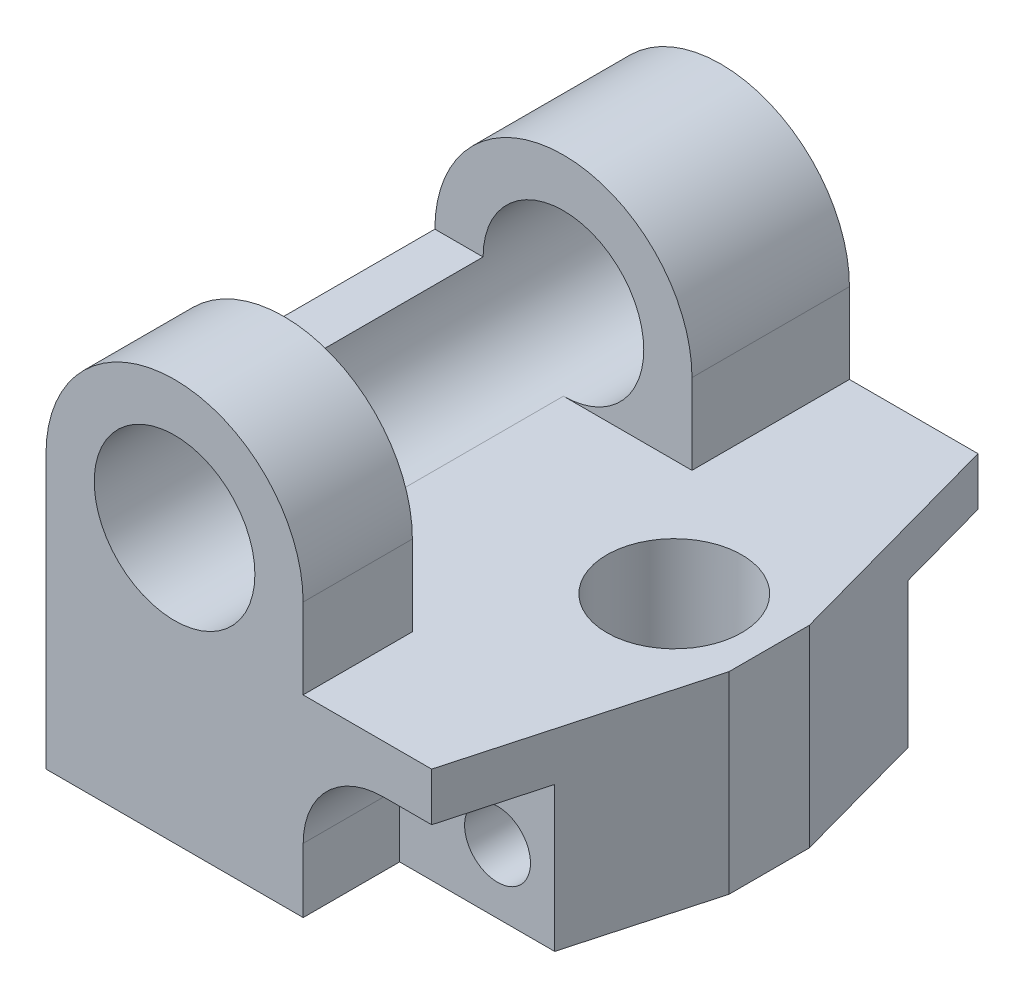
SolidWorks part; units mm, degrees
ref_plane "前视基准面" through (0, 0, 0) normal (0, 0, 1) x (1, 0, 0)
ref_plane "上视基准面" through (0, 0, 0) normal (0, 1, 0) x (1, 0, 0)
ref_plane "右视基准面" through (0, 0, 0) normal (1, 0, 0) x (0, 0, -1)
sketch "草图1" plane through (0, 0, 0) normal (0, 0, 1) x (1, 0, 0)
  line L0 (0, 0) -> (0, 2.5)
  line L2 (0, 0) -> (0, -6)
  line L3 (0, -6) -> (14, -6)
  line L4 (14, 0) -> (14, -6)
  line L5 (8, 2.5) -> (8, 0)
  line L6 (8, 0) -> (14, 0)
  circle A0 centre (4, 2.5) radius 2.5
  arc A1 (8, 2.5) -> (0, 2.5) centre (4, 2.5) ccw
  dimension "D1" = 14
  dimension "D2" = 6
extrude "凸台-拉伸1" add sketch "草图1" along normal mid plane 17
sketch "草图2" plane through (0, 0, 0) normal (0, 1, 0) x (1, 0, 0)
  line L0 (14, 1.25) -> (12, 8.5)
  line L1 (14, 8.5) -> (14, 1.25)
  line L2 (14, -1.25) -> (12, -8.5)
  line L12 (12, 8.5) -> (14, 8.5)
  line L14 (12, -8.5) -> (14, -8.5)
  line L15 (14, -8.5) -> (14, -1.25)
  line L16 (14, -1.25) -> (14.0089, -1.2243)
  line M5 (14, 8.5) -> (8, 8.5)
  line M7 (8, -8.5) -> (14, -8.5)
  line M8 (14, -8.5) -> (14, 8.5)
extrude "切除-拉伸1" cut sketch "草图2" against normal blind 17 contours L0 M8 M5 | L2 M8 M7 region at (13.3333, 0, -6.0833) region at (13.3333, 0, 6.0833)
sketch "草图3" plane through (0, 0, 8.5) normal (0, 0, 1) x (1, 0, 0)
  line L0 (12, -1.5) -> (8.0034, -1.5)
  line L1 (12, 0) -> (12, -6) construction
  line L2 (8.0034, -1.5) -> (8.0034, -6)
  line L3 (0, -6) -> (12, -6) construction
  line L4 (12, 0) -> (8, 0) construction
  line L5 (12, -1.5) -> (14.4473, -1.5)
  line L6 (14.4473, -1.5) -> (14.4473, -6.7822)
  line L7 (14.4473, -6.7822) -> (8.0034, -6.7822)
  line L8 (8.0034, -6.7822) -> (8.0034, -6)
  dimension "D1" = 1.5
extrude "切除-拉伸2" cut sketch "草图3" against normal blind 3
fillet "圆角1" radius 2.5 1 edges at (8.0034, -1.5, 7)
mirror "镜向1" about plane through (0, 0, 0) normal (0, 0, 1) of "切除-拉伸2", "圆角1"
sketch "草图4" plane through (0, 0, 0) normal (0, 1, 0) x (1, 0, 0)
  line L0 (14, -1.25) -> (14, 1.25) construction
  circle A0 centre (11.05, 0) radius 2.1
  dimension "D1" = 2.95
extrude "切除-拉伸3" cut sketch "草图4" against normal up to next
sketch "草图5" plane through (0, 0, 0) normal (0, 1, 0) x (1, 0, 0)
  line L0 (11.05, 2.1) -> (11.05, -8.5) construction
  line L1 (12, -8.5) -> (8, -8.5) construction
  circle A0 centre (11.05, 0) radius 2.1 construction
sketch "草图6" plane through (0, 0, 5.5) normal (0, 0, 1) x (1, 0, 0)
  line L0 (11.05, 0) -> (11.05, -6) construction
  line L1 (12.8276, -6) -> (8.0034, -6) construction
  line L2 (14, -6) -> (14, 0) construction
  line L3 (11.05, -4) -> (14, -4) construction
  dimension "D1" = 2.95
  dimension "D2" = 2
hole_wizard "M2.5 螺纹孔1" positions "草图8" profile "草图7" tap size "M2.5" standard "GB" end condition up to next
sketch "草图8" plane through (0, 0, 5.5) normal (0, 0, 1) x (1, 0, 0)
  point P0 (11.05, -4)
sketch "草图7" plane through (11.05, -4, 5.5) normal (1, 0, 0) x (0, -1, 0)
  line L0 (0, 0) -> (0, 3.4)
  line L1 (0, 3.4) -> (1.025, 3.4)
  line L2 (1.025, 3.4) -> (1.025, 0)
  line L5 (1.025, 0) -> (0, 0)
  line L11 (0, -6.35) -> (0, 107.95) construction
  dimension "通孔螺纹孔钻头直径" = 2.05
  dimension "通孔螺纹孔钻头深度" = 3.4
cosmetic thread "孔螺蚊线1" parameters "D2"=2.5
sketch "草图9" plane through (0, 0, -5.5) normal (0, 0, -1) x (-1, 0, 0)
  circle A0 centre (-11.05, -4) radius 1.425
extrude "切除-拉伸4" cut sketch "草图9" against normal up to next
sketch "草图10" plane through (0, 0, 0) normal (0, 0, 1) x (1, 0, 0)
  line L0 (0, 2.5) -> (1.5, 2.5)
  line L1 (4, 0) -> (8, 0)
  line L2 (8, 0) -> (8, 2.5)
  arc A0 (8, 2.5) -> (0, 2.5) centre (4, 2.5) ccw
  circle A1 centre (4, 2.5) radius 2.5 construction
  arc A2 (4, 0) -> (1.5, 2.5) centre (4, 2.5) ccw
extrude "切除-拉伸5" cut sketch "草图10" along normal blind 5.1
extrude "切除-拉伸6" cut sketch "草图10<2>" against normal blind 3.6
sketch "草图10<2>" plane through (0, 0, 0) normal (0, 0, 1) x (1, 0, 0) same geometry as "草图10"
